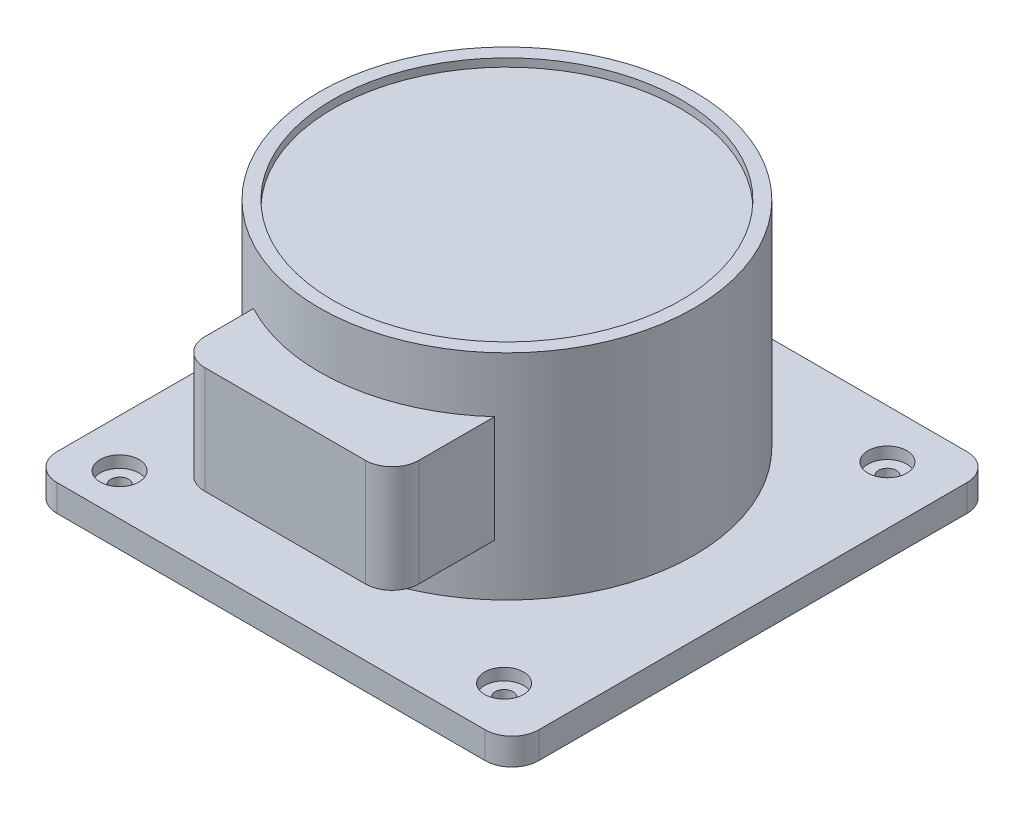
SolidWorks part; units mm, degrees
ref_plane "Front Plane" through (0, 0, 0) normal (0, 0, 1) x (1, 0, 0)
ref_plane "Top Plane" through (0, 0, 0) normal (0, 1, 0) x (1, 0, 0)
ref_plane "Right Plane" through (0, 0, 0) normal (1, 0, 0) x (0, 0, -1)
sketch "Sketch1" plane through (0, 0, 0) normal (0, 1, 0) x (1, 0, 0)
  line L1 (-139.5918, 84.4898) -> (40.4082, 84.4898)
  line L2 (-139.5918, 84.4898) -> (-139.5918, -95.5102)
  line L3 (-139.5918, -95.5102) -> (40.4082, -95.5102)
  line L4 (40.4082, 84.4898) -> (40.4082, -95.5102)
  dimension "D1" = 180
extrude "Boss-Extrude1" add sketch "Sketch1" along normal blind 10
sketch "Sketch2" plane through (0, 10, 0) normal (0, 1, 0) x (1, 0, 0)
  circle A0 centre (-57.0067, 0) radius 70
  dimension "D1" = 140
extrude "Boss-Extrude2" add sketch "Sketch2" along normal blind 80
sketch "Sketch3" plane through (0, 0, 0) normal (0, 0, 1) x (1, 0, 0)
  line L1 (-89.8939, 69.2885) -> (-9.8939, 69.2885)
  line L2 (-89.8939, 69.2885) -> (-89.8939, 29.2885)
  line L3 (-89.8939, 29.2885) -> (-9.8939, 29.2885)
  line L4 (-9.8939, 69.2885) -> (-9.8939, 29.2885)
  dimension "D1" = 40
  dimension "D2" = 80
extrude "Boss-Extrude3" add sketch "Sketch3" along normal blind 90
sketch "Sketch4" plane through (0, 90, 0) normal (0, 1, 0) x (1, 0, 0)
  circle A2 centre (-57.0067, 0) radius 65
  circle A3 centre (-57.0067, 0) radius 65
  dimension "D1" = 5
extrude "Cut-Extrude1" cut sketch "Sketch4" against normal blind 3
hole_wizard "CBORE for M6 Hex Head Bolt1" positions "Sketch7" profile "Sketch8" counterbore size "M6" standard "ANSI Metric" end condition through all
sketch "Sketch7" plane through (0, 10, 0) normal (0, 1, 0) x (1, 0, 0)
  point P0 (-121.7277, 66.3147)
  point P2 (18.8544, 66.3147)
  point P4 (18.8544, -76.9116)
  point P6 (-121.7277, -79.9964)
sketch "Sketch8" plane through (-121.7277, 10, -66.3147) normal (1, 0, 0) x (0, 0, 1)
  line L0 (0, 0) -> (0, 10)
  line L1 (0, 10) -> (3.3, 10)
  line L3 (3.3, 10) -> (3.3, 4.38)
  line L4 (3.3, 4.38) -> (7.275, 4.38)
  line L5 (7.275, 4.38) -> (7.275, 0)
  line L7 (7.275, 0) -> (0, 0)
  line L11 (0, -6.35) -> (0, 107.95) construction
  dimension "Thru Hole Dia." = 6.6
  dimension "Thru Hole Depth" = 10
  dimension "C'Bore Dia." = 14.55
  dimension "C'Bore Depth" = 4.38
fillet "Fillet1" radius 10 6 edges at (-9.8939, 49.2885, 90) (-89.8939, 49.2885, 90) (-139.5918, 5, -84.4898) (40.4082, 5, -84.4898) (40.4082, 5, 95.5102) (-139.5918, 5, 95.5102)
